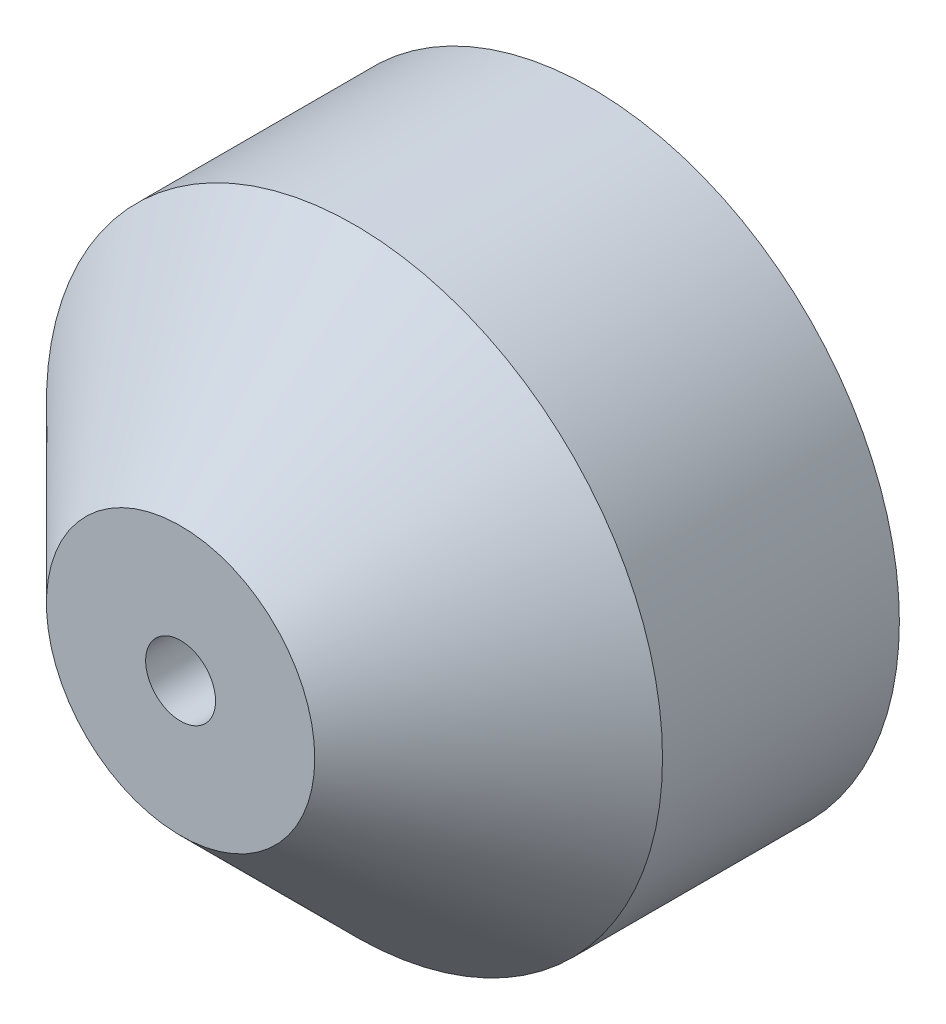
SolidWorks part; units mm, degrees
material "ABS"
ref_plane "Front Plane" through (0, 0, 0) normal (0, 0, 1) x (1, 0, 0)
ref_plane "Top Plane" through (0, 0, 0) normal (0, 1, 0) x (1, 0, 0)
ref_plane "Right Plane" through (0, 0, 0) normal (1, 0, 0) x (0, 0, -1)
sketch "Sketch1" plane through (0, 0, 0) normal (0, 0, 1) x (1, 0, 0)
  circle A0 centre (0, 0) radius 22.5
  dimension "D1" = 45
extrude "Boss-Extrude1" add sketch "Sketch1" against normal blind 30
sketch "Sketch2" plane through (0, 0, -30) normal (0, 0, -1) x (-1, 0, 0)
  circle A0 centre (0, 0) radius 17.5
  dimension "D1" = 35
extrude "Cut-Extrude1" cut sketch "Sketch2" against normal blind 15
sketch "Sketch5" plane through (0, 0, 0) normal (0, 0, 1) x (1, 0, 0)
  point P0 (0, 0)
hole_wizard "1/4-20 Tapped Hole1" positions "Sketch7" profile "Sketch8" tap size "1/4-20" standard "ANSI Inch" end condition up to next
sketch "Sketch7" plane through (0, 0, 0) normal (0, 0, 1) x (1, 0, 0)
  point P0 (0, 0)
sketch "Sketch8" plane through (0, 0, 0) normal (1, 0, 0) x (0, -1, 0)
  line L0 (0, 0) -> (0, 15)
  line L1 (0, 15) -> (2.5527, 15)
  line L2 (2.5527, 15) -> (2.5527, 0)
  line L5 (2.5527, 0) -> (0, 0)
  line L11 (0, -6.35) -> (0, 107.95) construction
  dimension "Thru Tap Drill Dia." = 5.1054
  dimension "Thru Tap Drill Depth" = 15
cosmetic thread "Hole Thread1"
chamfer "Chamfer1" distance 12.7 angle 45 1 edges at (22.5, 0, 0)
